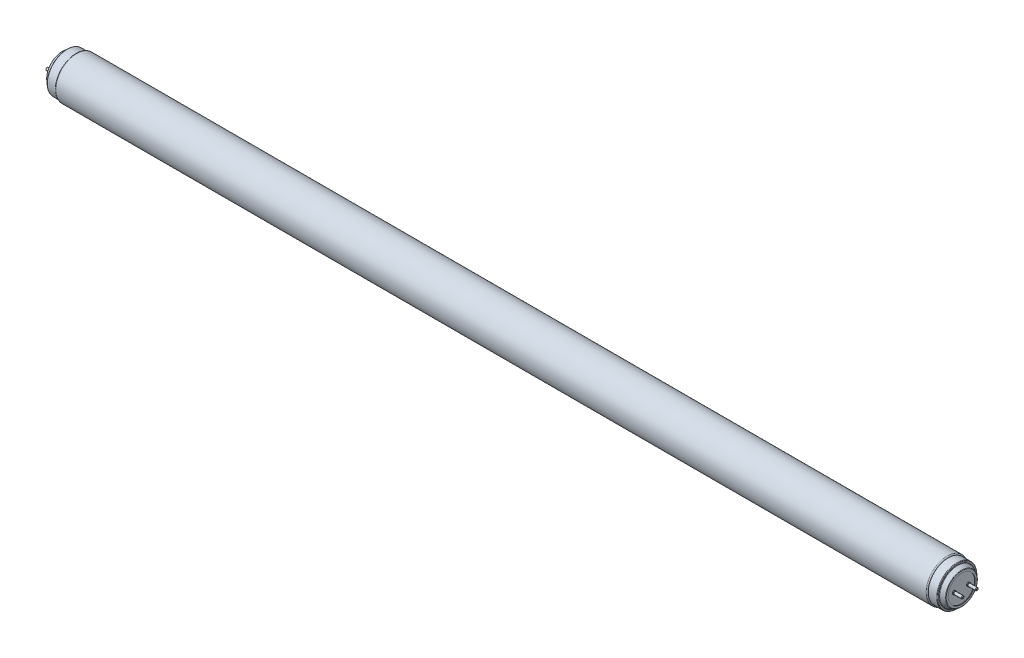
SolidWorks part; units mm, degrees
ref_plane "Front Plane" through (0, 0, 0) normal (0, 0, 1) x (1, 0, 0)
ref_plane "Top Plane" through (0, 0, 0) normal (0, 1, 0) x (1, 0, 0)
ref_plane "Right Plane" through (0, 0, 0) normal (1, 0, 0) x (0, 0, -1)
sketch "Sketch1" plane through (0, 0, 0) normal (0, 0, 1) x (1, 0, 0)
  line L0 (0, -17.75) -> (-7.5, -17.75)
  line L1 (-8, -17.25) -> (-8, -16.309)
  line L2 (-8.2764, -15.8618) -> (-11.7236, -14.1382)
  line L3 (-12, -13.691) -> (-12, -12)
  line L4 (-12, -12) -> (-11.5, -12)
  line L5 (-11.5, -12) -> (-11.5, 0)
  line L6 (-11.5, 0) -> (0, 0)
  line L7 (0, 0) -> (0, -17.75) construction
  line L8 (0.95, -18.7) -> (775.05, -18.7)
  line L9 (388, -18.7) -> (388, 0) construction
  line L10 (0, 0) -> (776, 0)
  line L11 (776, 0) -> (776, -17.75) construction
  line L12 (787.5, 0) -> (776, 0)
  line L13 (787.5, -12) -> (787.5, 0)
  line L14 (788, -12) -> (787.5, -12)
  line L15 (788, -13.691) -> (788, -12)
  line L16 (784.2764, -15.8618) -> (787.7236, -14.1382)
  line L17 (784, -17.25) -> (784, -16.309)
  line L18 (776, -17.75) -> (783.5, -17.75)
  line L19 (-11.5, 0) -> (-47.7314, 0) construction
  arc A0 (0, -17.75) -> (0.95, -18.7) centre (0.95, -17.75) ccw
  arc A1 (-7.5, -17.75) -> (-8, -17.25) centre (-7.5, -17.25) cw
  arc A2 (-8, -16.309) -> (-8.2764, -15.8618) centre (-8.5, -16.309) ccw
  arc A3 (-11.7236, -14.1382) -> (-12, -13.691) centre (-11.5, -13.691) cw
  arc A4 (787.7236, -14.1382) -> (788, -13.691) centre (787.5, -13.691) ccw
  arc A5 (784, -16.309) -> (784.2764, -15.8618) centre (784.5, -16.309) cw
  arc A6 (783.5, -17.75) -> (784, -17.25) centre (783.5, -17.25) ccw
  arc A7 (776, -17.75) -> (775.05, -18.7) centre (775.05, -17.75) cw
  point P15 (-8, -17.75)
  point P18 (-8, -16)
  point P21 (-12, -14)
  point P38 (788, -14)
  point P39 (784, -16)
  point P40 (784, -17.75)
  dimension "D9" = 0.5
  dimension "D1" = 17.75
  dimension "D2" = 8
  dimension "D3" = 14
  dimension "D4" = 12
  dimension "D5" = 0.5
  dimension "D6" = 12
  dimension "D7" = 16
  dimension "D8" = 18.7
  dimension "D10" = 800
revolve "Revolve1" add sketch "Sketch1" angle 360 about L19
sketch "Sketch2" plane through (-11.5, 0, 0) normal (-1, 0, 0) x (0, 0, 1)
  line L0 (-6.3, 0) -> (6.3, 0) construction
  circle A0 centre (-6.3, 0) radius 1.2
  circle A1 centre (6.3, 0) radius 1.2
  dimension "D1" = 2.4
  dimension "D2" = 15
extrude "Extrude1" add sketch "Sketch2" along normal blind 8
sketch "Sketch3" plane through (-11.5, 0, 0) normal (-1, 0, 0) x (0, 0, 1)
  circle A0 centre (-6.3, 0) radius 1.5
  circle A1 centre (6.3, 0) radius 1.5
  dimension "D1" = 3
  dimension "D2" = 3
extrude "Extrude2" add sketch "Sketch3" along normal blind 1
sketch "Sketch4" plane through (787.5, 0, 0) normal (1, 0, 0) x (0, 0, -1)
  circle A0 centre (6.3, 0) radius 1.2 construction
  circle A1 centre (-6.3, 0) radius 1.2 construction
  circle A2 centre (6.3, 0) radius 1.2
  circle A3 centre (-6.3, 0) radius 1.2
extrude "Extrude3" add sketch "Sketch4" along normal blind 8
sketch "Sketch5" plane through (787.5, 0, 0) normal (1, 0, 0) x (0, 0, -1)
  circle A0 centre (6.3, 0) radius 1.5 construction
  circle A1 centre (-6.3, 0) radius 1.5 construction
  circle A2 centre (6.3, 0) radius 1.5
  circle A3 centre (-6.3, 0) radius 1.5
extrude "Extrude4" add sketch "Sketch5" along normal blind 1
chamfer "Chamfer1" distance 0.3 angle 45 4 edges at (-12.5, 0, 7.8) (-12.5, 0, -4.8) (788.5, 0, -7.8) (788.5, 0, 4.8)
chamfer "Chamfer2" distance 0.5 angle 45 4 edges at (-19.5, 0, -5.1) (-19.5, 0, 7.5) (795.5, 0, -7.5) (795.5, 0, 5.1)
